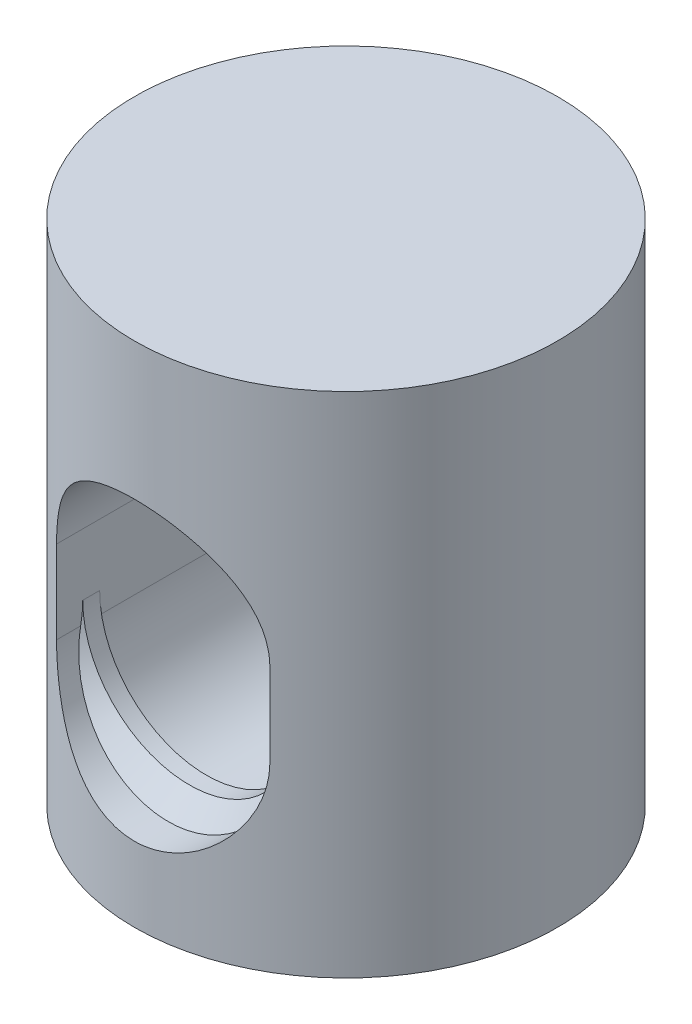
SolidWorks part; units mm, degrees
material "Alloy Steel"
ref_plane "Front Plane" through (0, 0, 0) normal (0, 0, 1) x (1, 0, 0)
ref_plane "Top Plane" through (0, 0, 0) normal (0, 1, 0) x (1, 0, 0)
ref_plane "Right Plane" through (0, 0, 0) normal (1, 0, 0) x (0, 0, -1)
sketch "Sketch2" plane through (0, 0, 0) normal (0, 1, 0) x (1, 0, 0)
  circle A0 centre (0, 0) radius 6.35
  dimension "D1" = 12.7
extrude "Boss-Extrude1" add sketch "Sketch2" along normal blind 15.24
ref_plane "Plane1" through (0, 0, 6.35) normal (0, 0, 1) x (1, 0, 0)
sketch "Sketch4" plane through (0, 0, 6.35) normal (0, 0, 1) x (1, 0, 0)
  line L0 (0, 0) -> (0, 15.24) construction
  line L1 (6.35, 15.24) -> (-6.35, 15.24) construction
  line L2 (0, 5.4408) -> (0, 7.93) construction
  line L3 (-3.2004, 5.4408) -> (-3.2004, 7.93)
  line L4 (3.2004, 5.4408) -> (3.2004, 7.93)
  arc A0 (-3.2004, 5.4408) -> (3.2004, 5.4408) centre (0, 5.4408) ccw
  arc A1 (3.2004, 7.93) -> (-3.2004, 7.93) centre (0, 7.93) ccw
  circle A2 centre (0, 6.0758) radius 3.2004
  point P7 (0, 6.6854)
  point P12 (0, 11.1304)
  point P13 (0, 2.2404)
  dimension "D3" = 0.635
  dimension "D1" = 6.4008
  dimension "D2" = 8.89
extrude "Cut-Extrude1" cut sketch "Sketch4" against normal blind 0.889 contours A0 L4 A1 L3
extrude "Cut-Extrude2" cut sketch "Sketch4<3>" against normal up to next contours A1 A2 region at (0, 6.0758, 6.35)
sketch "Sketch4<3>" plane through (0, 0, 6.35) normal (0, 0, 1) x (1, 0, 0) same geometry as "Sketch4"
extrude "Cut-Extrude3" cut sketch "Sketch4<4>" against normal up to next contours A2 L4 A1 L3 region at (0, 9.5164, 6.35)
sketch "Sketch4<4>" plane through (0, 0, 6.35) normal (0, 0, 1) x (1, 0, 0) same geometry as "Sketch4"
ref_plane "Plane2" through (0, 0, 4.191) normal (0, 0, 1) x (1, 0, 0)
extrude "Cut-Extrude4" cut sketch "Sketch4<5>" against normal up to next from surface contours A0 L4 A1 L3 starting at plane "Plane2"
sketch "Sketch4<5>" plane through (0, 0, 6.35) normal (0, 0, 1) x (1, 0, 0) same geometry as "Sketch4"
chamfer "Chamfer1" distance 0.762 angle 45 1 edges at (0, 2.8754, 5.461)
